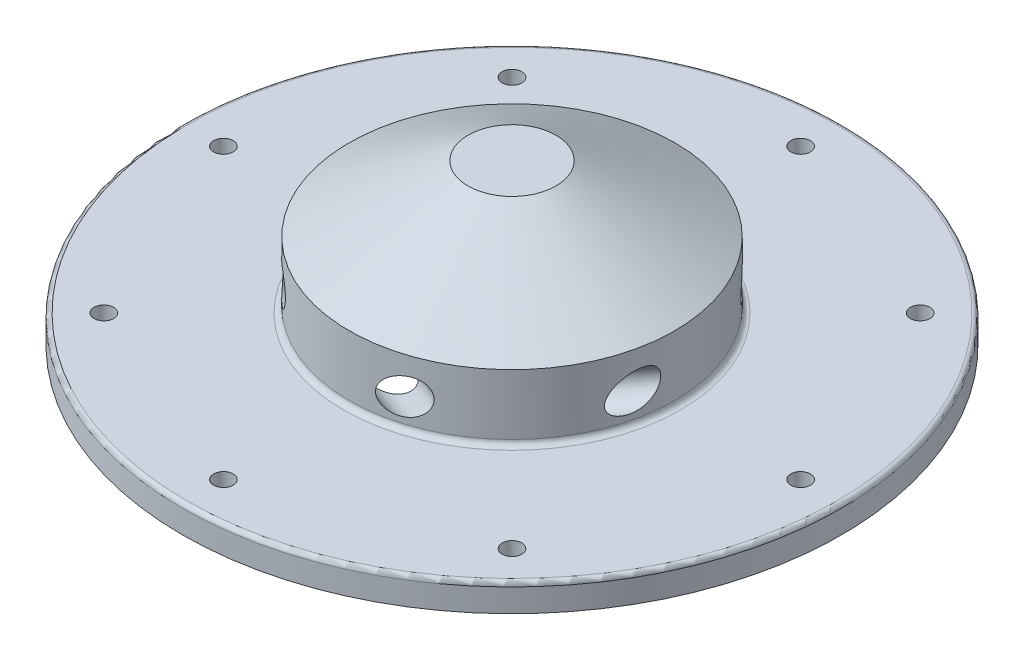
SolidWorks part; units mm, degrees
material "7075-T6 (SN)"
ref_plane "Front Plane" through (0, 0, 0) normal (0, 0, 1) x (1, 0, 0)
ref_plane "Top Plane" through (0, 0, 0) normal (0, 1, 0) x (1, 0, 0)
ref_plane "Right Plane" through (0, 0, 0) normal (1, 0, 0) x (0, 0, -1)
sketch "Sketch2" plane through (0, 0, 0) normal (0, 1, 0) x (1, 0, 0)
  circle A0 centre (0, 0) radius 38.0682
  dimension "D1" = 76.1365
extrude "Boss-Extrude1" add sketch "Sketch2" along normal blind 3.175
hole_wizard "Tap Drill for #4-40 Tap1" positions "Sketch3" profile "Sketch4" hole size "#4-40" standard "ANSI Inch" end condition through all
sketch "Sketch3" plane through (0, 0, 0) normal (0, -1, 0) x (-1, 0, 0)
  point P0 (0, -33.3375)
  dimension "D1" = 33.3375
sketch "Sketch4" plane through (0, 0, 33.3375) normal (1, 0, 0) x (0, 0, -1)
  line L0 (0, 0) -> (0, 3.175)
  line L1 (0, 3.175) -> (1.1303, 3.175)
  line L2 (1.1303, 3.175) -> (1.1303, 0)
  line L5 (1.1303, 0) -> (0, 0)
  line L11 (0, -6.35) -> (0, 107.95) construction
  dimension "Thru Hole Dia." = 2.2606
  dimension "Thru Hole Depth" = 3.175
pattern_circular "CirPattern1" count 8 over 360 about axis through (0, 0, 0) along (0, 1, 0) of "Tap Drill for #4-40 Tap1"
sketch "Sketch5" plane through (0, 3.175, 0) normal (0, 1, 0) x (1, 0, 0)
  circle A0 centre (0, 0) radius 28.575
  dimension "D1" = 57.15
sketch "Sketch7" plane through (0, 3.175, 0) normal (0, 1, 0) x (1, 0, 0)
  circle A0 centre (0, 0) radius 18.81
  dimension "D1" = 37.62
extrude "Boss-Extrude2" add sketch "Sketch7" along normal blind 7.62
sketch "Sketch8" plane through (0, 0, 0) normal (0, -1, 0) x (1, 0, 0)
  circle A0 centre (0, 0) radius 15
  dimension "D1" = 30
extrude "Cut-Extrude1" cut sketch "Sketch8" against normal blind 8.89
sketch "Sketch13" plane through (0, 10.795, 0) normal (0, 1, 0) x (1, 0, 0)
  circle A0 centre (0, 0) radius 18.81
  circle A1 centre (0, 0) radius 18.81 construction
  dimension "D1" = 0
ref_plane "Plane2" through (0, 18.415, 0) normal (0, 1, 0) x (1, 0, 0)
sketch "Sketch14" plane through (0, 18.415, 0) normal (0, 1, 0) x (1, 0, 0)
  circle A0 centre (0, 0) radius 5.08
  dimension "D1" = 10.16
loft "Loft2" add profiles "Sketch14", "Sketch13" connector at (-0.0647, 18.415, 5.0796) connector at (0, 10.795, 18.81)
fillet "Fillet1" radius 0.635 1 edges at (0, 8.89, -15)
fillet "Fillet3" radius 0.5 1 edges at (0, 3.175, 38.0682)
ref_plane "Plane4" through (0, 7.62, 0) normal (0, 1, 0) x (1, 0, 0)
fillet "Fillet2" radius 0.635 1 edges at (0, 3.175, 18.81)
ref_axis "Axis1" through (41.91, 7.62, 0) along (-1, 0, 0)
ref_plane "Plane3" through (0, 0.5104, 1.905) normal (0, 0.2588, 0.9659) x (-1, 0, 0)
sketch "Sketch16" plane through (0, 0.5104, 1.905) normal (0, 0.2588, 0.9659) x (-1, 0, 0)
  circle A0 centre (12.71, -2.7899) radius 1.98
  dimension "D1" = 3.96
  dimension "D2" = 12.71
  dimension "D3" = 2.7899
extrude "Cut-Extrude2" cut sketch "Sketch16" along normal through all
pattern_circular "CirPattern2" count 6 over 360 about axis through (0, 10.795, 0) along (0, 1, 0) of "Cut-Extrude2"
